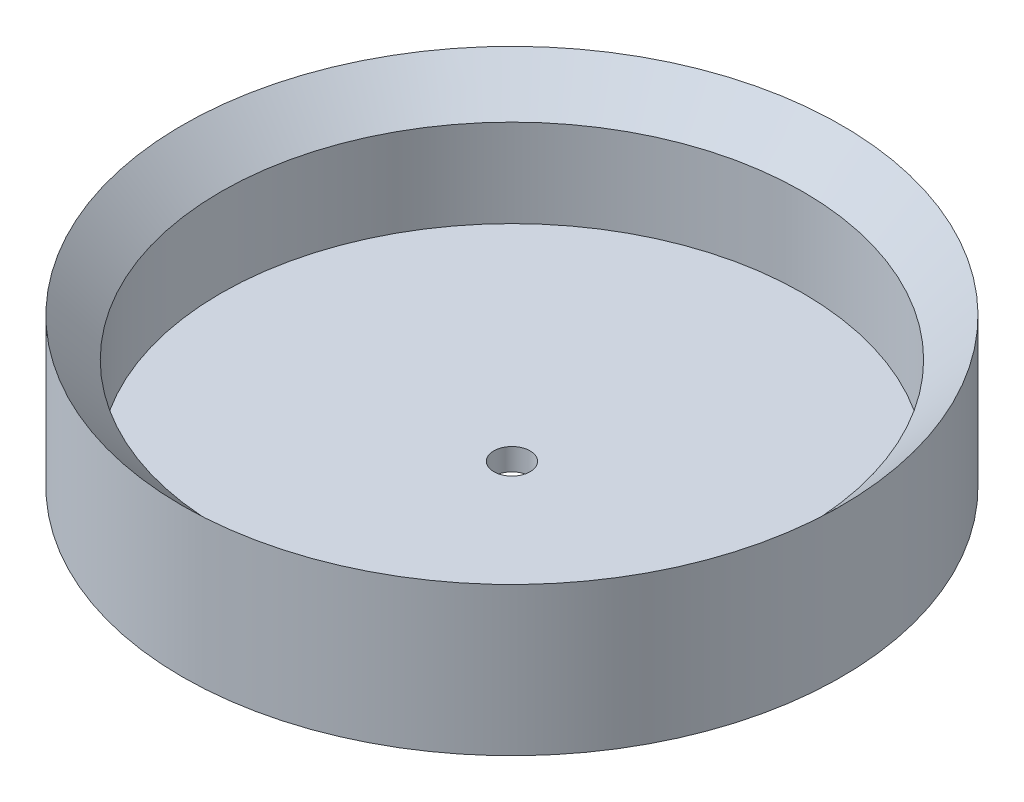
SolidWorks part; units mm, degrees
ref_plane "前视基准面" through (0, 0, 0) normal (0, 0, 1) x (1, 0, 0)
ref_plane "上视基准面" through (0, 0, 0) normal (0, 1, 0) x (1, 0, 0)
ref_plane "右视基准面" through (0, 0, 0) normal (1, 0, 0) x (0, 0, -1)
other "Configuration Table"
sketch "草图1" plane through (0, 0, 0) normal (0, 1, 0) x (1, 0, 0)
  circle A0 centre (0, 0) radius 30
  circle A1 centre (0, 0) radius 26.5
  dimension "D1" = 60
  dimension "D2" = 53
extrude "凸台-拉伸1" add sketch "草图1" along normal blind 15
sketch "草图2" plane through (0, 0, 0) normal (0, -1, 0) x (1, 0, 0)
  circle A1 centre (0, 0) radius 30
  circle A2 centre (0, 0) radius 30
  dimension "D1" = 0
extrude "凸台-拉伸2" add sketch "草图2" against normal blind 2
chamfer "倒角1" distance 5 angle 45 1 edges at (0, 15, 26.5)
sketch "草图3" plane through (0, 2, 0) normal (0, 1, 0) x (1, 0, 0)
  circle A0 centre (0, 0) radius 1.65
  circle A1 centre (0, 0) radius 26.5
  circle A2 centre (0, 0) radius 26.5
  dimension "D2" = 3.3
  dimension "D1" = 0
extrude "切除-拉伸1" cut sketch "草图3" against normal through all contours A0 region at (0, 2, 0)
